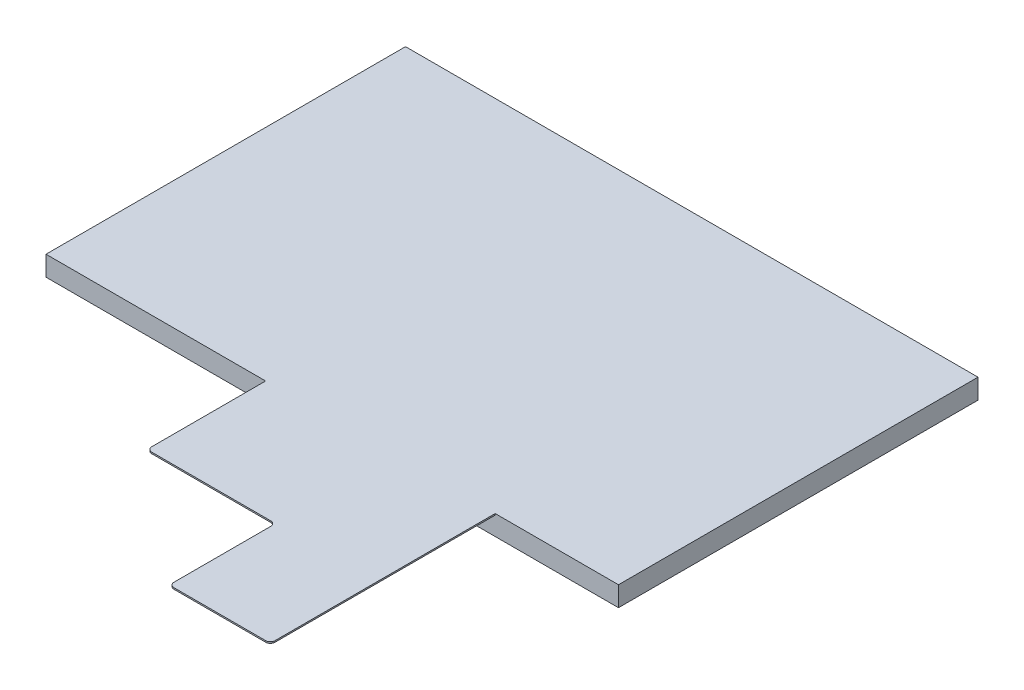
SolidWorks part; units mm, degrees
ref_plane "Front Plane" through (0, 0, 0) normal (0, 0, 1) x (1, 0, 0)
ref_plane "Top Plane" through (0, 0, 0) normal (0, 1, 0) x (1, 0, 0)
ref_plane "Right Plane" through (0, 0, 0) normal (1, 0, 0) x (0, 0, -1)
sketch "Sketch1" plane through (0, 0, 0) normal (0, 1, 0) x (1, 0, 0)
  line L1 (0, 0) -> (120.7, 0)
  line L2 (0, 0) -> (0, -75.8)
  line L3 (0, -75.8) -> (120.7, -75.8)
  line L4 (120.7, 0) -> (120.7, -75.8)
  dimension "D1" = 75.8
  dimension "D2" = 120.7
extrude "Boss-Extrude1" add sketch "Sketch1" along normal blind 4.2
sketch "Sketch2" plane through (0, 4.2, 0) normal (0, 1, 0) x (1, 0, 0)
  line L0 (0, -75.8) -> (120.7, -75.8) construction
  line L1 (46.3, -75.8) -> (94.7, -75.8)
  line L2 (46.3, -75.8) -> (46.3, -123.2)
  line L3 (46.3, -123.2) -> (94.7, -123.2)
  line L4 (94.7, -75.8) -> (94.7, -123.2)
  line L6 (120.7, -75.8) -> (120.7, 0) construction
  dimension "D2" = 47.4
  dimension "D3" = 48.4
  dimension "D1" = 26
extrude "Boss-Extrude2" add sketch "Sketch2" against normal blind 0.3
sketch "Sketch4" plane through (0, 3.9, 0) normal (0, -1, 0) x (1, 0, 0)
  line L1 (46.3, 123.2) -> (73.38, 123.2)
  line L2 (46.3, 123.2) -> (46.3, 100.79)
  line L3 (46.3, 100.79) -> (73.38, 100.79)
  line L4 (73.38, 123.2) -> (73.38, 100.79)
  dimension "D1" = 27.08
  dimension "D2" = 22.41
extrude "Cut-Extrude1" cut sketch "Sketch4" against normal blind 0.3
fillet "Fillet2" radius 1 4 edges at (46.3, 4.05, 100.79) (73.38, 4.05, 100.79) (73.38, 4.05, 123.2) (94.7, 4.05, 123.2)
equation "\"D3@Sketch2\"=20.5+27.9"
